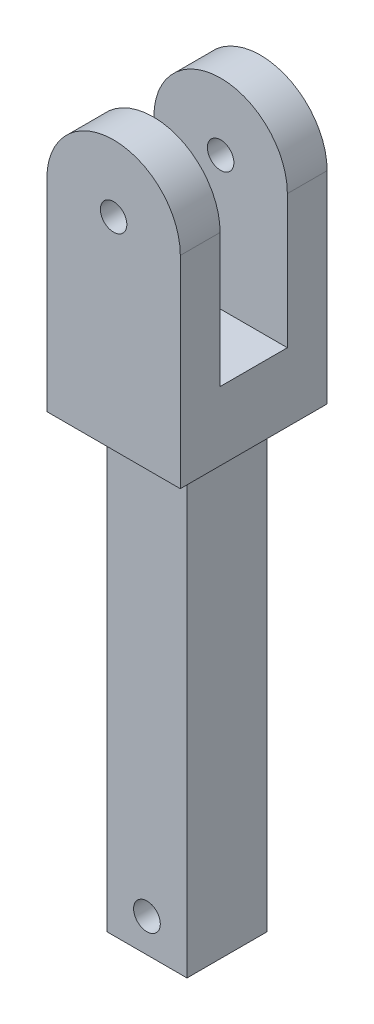
SolidWorks part; units mm, degrees
ref_plane "前基準面" through (0, 0, 0) normal (0, 0, 1) x (1, 0, 0)
ref_plane "上基準面" through (0, 0, 0) normal (0, 1, 0) x (1, 0, 0)
ref_plane "右基準面" through (0, 0, 0) normal (1, 0, 0) x (0, 0, -1)
sketch "草圖1" plane through (0, 0, 0) normal (0, 0, 1) x (1, 0, 0)
  line L0 (0, 0) -> (0, -11.05)
  line L1 (-10, 0) -> (-10, -30.2764)
  line L3 (10, -30.2764) -> (10, 0)
  line L4 (-10, -30.2764) -> (10, -30.2764)
  circle A1 centre (0, 0) radius 1.985
  arc A2 (10, 0) -> (-10, 0) centre (0, 0) ccw
  dimension "D1" = 11.05
  dimension "D2" = 3.97
  dimension "D3" = 20
extrude "填料-伸長1" add sketch "草圖1" along normal blind 12 contours L3 A2 L1 A1 region at (0, -11.3298, 0)
sketch "草圖2" plane through (10, 0, 0) normal (1, 0, 0) x (0, 0, -1)
  line L0 (-12, 0) -> (-9.1, 0)
  line L1 (-12, 0) -> (0, 0) construction
  line L2 (-12, 10) -> (-12, 0) construction
  line L3 (0, 0) -> (-2.9, 0)
  line L4 (-6, 0) -> (-3, 0)
  line L5 (-6, 0) -> (-9, 0)
  line L6 (-9, 0) -> (-9, 15.7808)
  line L7 (-9, 15.7808) -> (-3, 15.7808)
  line L8 (-3, 15.7808) -> (-3, 0)
  line L9 (-3, 0) -> (-3, -20)
  line L10 (-9, 0) -> (-8.6005, -20)
  line L11 (-8.6005, -20) -> (-3, -20)
  line M8 (0, 0) -> (-12, 0)
  dimension "D1" = 2.9
  dimension "D2" = 2.9
  dimension "D3" = 3
  dimension "D4" = 3
  dimension "D5" = 20
extrude "除料-伸長1" cut sketch "草圖2" against normal through all contours L8 L7 L6 M8 | L10 L11 L9 M8 region at (10, 7.8904, 6) region at (10, -9.8852, 5.9013)
sketch "草圖11" plane through (10, 0, 0) normal (1, 0, 0) x (0, 0, -1)
  line L0 (-9, 0) -> (-9, -20)
  line L1 (-9, -20) -> (-8.6005, -20)
  line L2 (-9, 0) -> (-8.6005, -20)
extrude "除料-伸長6" cut sketch "草圖11" against normal through all
sketch "草圖12" plane through (0, 0, 12) normal (0, 0, 1) x (1, 0, 0)
  line L0 (-10, 0) -> (-10, -30.2764)
  line L1 (-10, -30.2764) -> (10, -30.2764)
  line L2 (10, -30.2764) -> (10, 0)
  circle A0 centre (0, 0) radius 1.45
  circle A1 centre (0, 0) radius 10
  circle M1 centre (0, 0) radius 1.985
  line M2 (10, -30.2764) -> (10, 0)
  arc M3 (10, 0) -> (-10, 0) centre (0, 0) ccw
  line M4 (-10, 0) -> (-10, -30.2764)
  line M5 (-10, -30.2764) -> (10, -30.2764)
extrude "填料-伸長11" add sketch "草圖12" along normal blind 5 contours A1 M3 M1 | A1 M4 M5 M2 region at (0, -18.9541, 12) region at (0, 9.7172, 12)
sketch "草圖13" plane through (0, 0, 0) normal (0, 0, -1) x (-1, 0, 0)
  line L0 (-10, 0) -> (-10, -30.2764)
  line L1 (-10, -30.2764) -> (10, -30.2764)
  line L2 (10, 0) -> (10, -30.2764) construction
  line L3 (10, -30.2764) -> (-10, -30.2764) construction
  line L4 (10, -30.2764) -> (10, 0)
  circle A0 centre (0, 0) radius 1.45
  circle A1 centre (0, 0) radius 10
  circle M1 centre (0, 0) radius 1.985
  line M2 (-10, 0) -> (-10, -30.2764)
  line M3 (-10, -30.2764) -> (10, -30.2764)
  line M4 (10, -30.2764) -> (10, 0)
  arc M5 (10, 0) -> (-10, 0) centre (0, 0) ccw
extrude "填料-伸長12" add sketch "草圖13" along normal blind 5 contours A1 M5 M1 | A1 M2 M3 M4 region at (0, -18.9541, 0) region at (0, 9.7172, 0)
sketch "草圖14" plane through (-10, 0, 0) normal (-1, 0, 0) x (0, 0, 1)
  line L0 (3, -20) -> (0.96, -20)
  line L1 (0.96, -20) -> (0.96, 10)
  line L2 (3, 10) -> (-5, 10) construction
  line L3 (0.96, 10) -> (3, 10)
  line L5 (3, 10) -> (11.04, 10)
  line L6 (9, -20) -> (11.04, -20)
  line L7 (11.04, -20) -> (11.04, 10)
  line L8 (17, 10) -> (9, 10) construction
  line L9 (0.96, 10) -> (11.04, 10)
  line L10 (11.04, -20) -> (0.96, -20)
  line L11 (0.96, 10) -> (0.96, -20)
  line L12 (0.96, 10) -> (11.04, 10)
  line M7 (9, 0) -> (9, -20)
  line M8 (9, -20) -> (3, -20)
  line M9 (3, -20) -> (3, 0)
  line M10 (3, 0) -> (-5, 0)
  line M14 (17, 0) -> (9, 0)
  dimension "D1" = 2.04
  dimension "D2" = 2.04
extrude "除料-伸長7" cut sketch "草圖14" against normal through all contours L7 L5 L3 L1 M14 M10 M9 M8 M7 | L1 L0 M9 M10 | L6 L7 M14 M7 region at (-10, -3.1522, 6) region at (-10, -10, 1.98) region at (-10, -10, 10.02)
sketch "草圖15" plane through (0, -30.2764, 0) normal (0, -1, 0) x (1, 0, 0)
  line L0 (-10, 6) -> (10, 6)
  line L1 (-10, 17) -> (-10, -5) construction
  line L2 (10, 17) -> (10, -5) construction
  line L3 (0, 17) -> (0, -5)
  line L4 (-10, 17) -> (10, 17) construction
  line L5 (10, -5) -> (-10, -5) construction
  line L7 (-6, 0) -> (6, 0)
  line L8 (-6, 0) -> (-6, 12)
  line L9 (-6, 12) -> (6, 12)
  line L10 (6, 0) -> (6, 12)
  line L11 (-6, 0) -> (6, 12) construction
  line L12 (-6, 12) -> (6, 0) construction
  point P12 (0, 6)
  dimension "D1" = 12
  dimension "D2" = 12
extrude "填料-伸長13" add sketch "草圖15" along normal blind 68 contours L0 L10 L9 L3 | L9 L8 L0 L3 | L7 L10 L0 L3 | L8 L7 L3 L0 region at (-3, -30.2764, 9) region at (-3, -30.2764, 3) region at (3, -30.2764, 9) region at (3, -30.2764, 3)
sketch "草圖17" plane through (0, 0, 0) normal (0, 0, -1) x (-1, 0, 0)
  line L0 (0, -98.2764) -> (0, -93.2764)
  line L1 (6, -98.2764) -> (-6, -98.2764) construction
  circle A0 centre (0, -93.2764) radius 2
  dimension "D2" = 4
  dimension "D1" = 5
extrude "除料-伸長8" cut sketch "草圖17" against normal through all contours A0 region at (-1.3742, -94.6506, 0)
